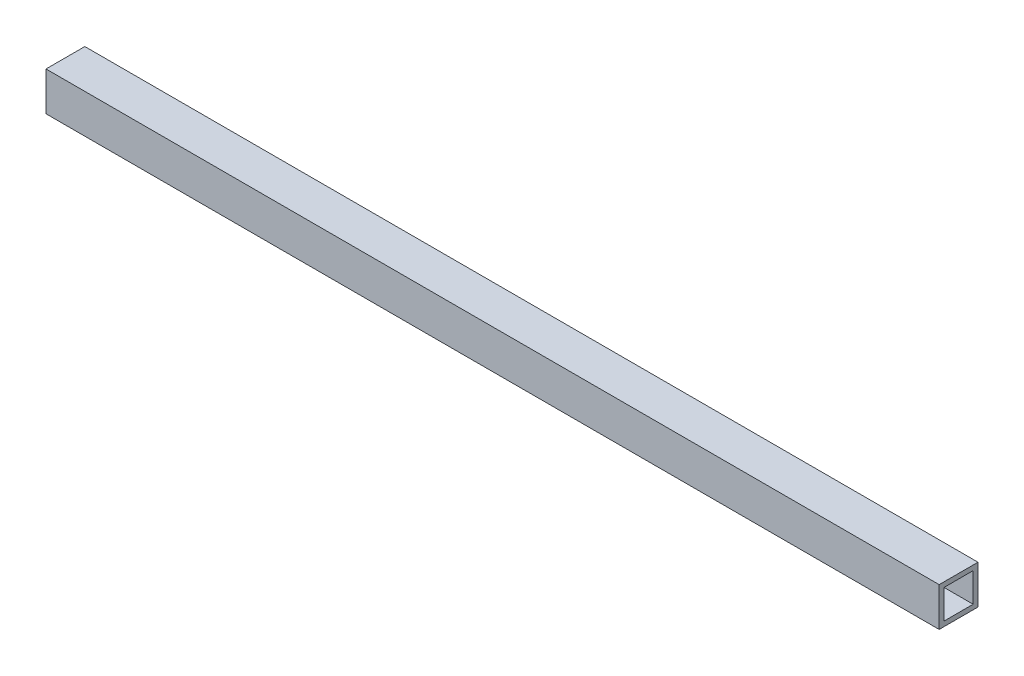
SolidWorks part; units mm, degrees
ref_plane "Front Plane" through (0, 0, 0) normal (0, 0, 1) x (1, 0, 0)
ref_plane "Top Plane" through (0, 0, 0) normal (0, 1, 0) x (1, 0, 0)
ref_plane "Right Plane" through (0, 0, 0) normal (1, 0, 0) x (0, 0, -1)
sketch "Sketch1" plane through (0, 0, 0) normal (1, 0, 0) x (0, 0, -1)
  line L1 (0, 0) -> (19.05, 0)
  line L2 (0, 0) -> (0, 19.05)
  line L3 (0, 19.05) -> (19.05, 19.05)
  line L4 (19.05, 0) -> (19.05, 19.05)
  dimension "D1" = 19.05
  dimension "D2" = 19.05
extrude "Extrude-Thin1" add sketch "Sketch1" along normal blind 584.2 thin thin type one direction wall 3.175
